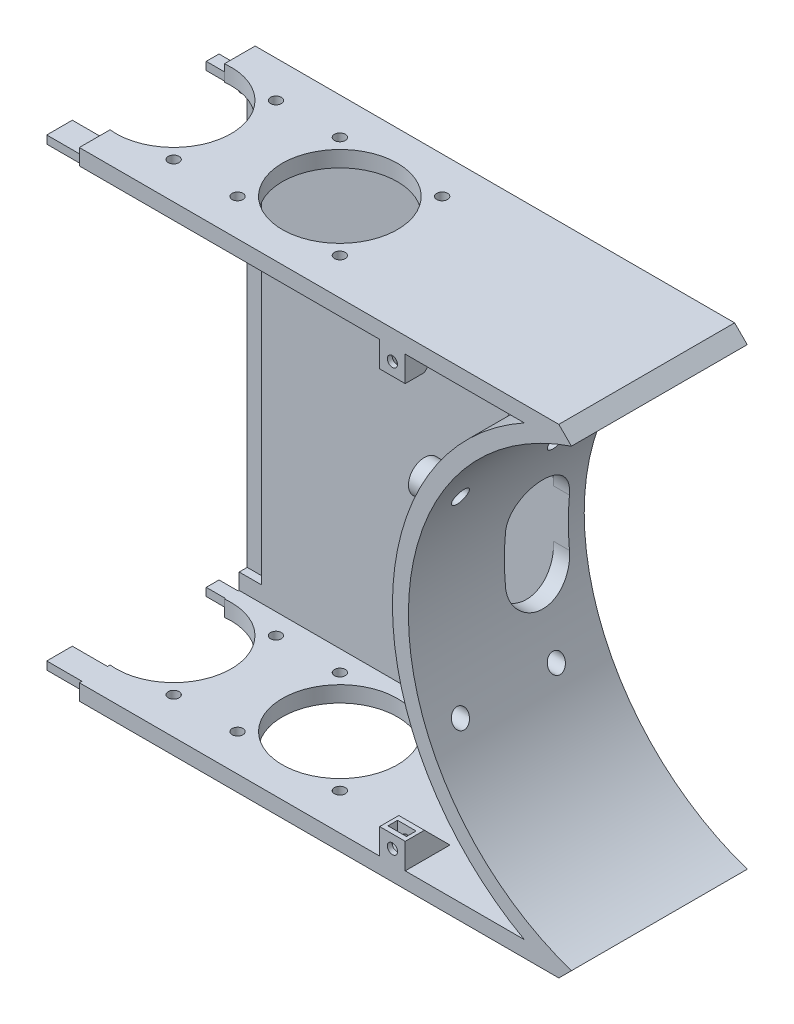
SolidWorks part; units mm, degrees
material "PLA"
ref_plane "Alzado" through (0, 0, 0) normal (0, 0, 1) x (1, 0, 0)
ref_plane "Planta" through (0, 0, 0) normal (0, 1, 0) x (1, 0, 0)
ref_plane "Vista lateral" through (0, 0, 0) normal (1, 0, 0) x (0, 0, -1)
sketch "Croquis1" plane through (0, 0, 0) normal (0, 0, 1) x (1, 0, 0)
  line L0 (-327.9437, 75) -> (-327.9437, -75)
  line L1 (-327.9437, 75) -> (-27.9437, 75)
  line L2 (-27.9437, 75) -> (-24, 71.0563)
  line L3 (-327.9437, -75) -> (-27.9437, -75)
  line L4 (-27.9437, -75) -> (-24, -71.0563)
  circle A0 centre (0, 0) radius 75 construction
  arc A1 (-24, 71.0563) -> (-24, -71.0563) centre (0, 0) ccw
  point P6 (-327.9437, 0)
  point P11 (-75, 0)
  dimension "D1" = 150
  dimension "D2" = 150
  dimension "D3" = 300
  dimension "D4" = 135
  dimension "D5" = 24
extrude "Saliente-Extruir1" add sketch "Croquis1" along normal blind 55
sketch "Croquis2" plane through (0, 0, 55) normal (0, 0, 1) x (1, 0, 0)
  line L2 (-27.9437, 70) -> (-327.9437, 70)
  line L3 (-38.7298, 70) -> (-322.9437, 70)
  line L5 (-322.9437, 75) -> (-322.9437, -75)
  line L6 (-322.9437, 70) -> (-322.9437, -70)
  line L8 (-327.9437, -70) -> (-27.9437, -70)
  line L9 (-322.9437, -70) -> (-38.7298, -70)
  arc A2 (-25.6, 75.7934) -> (-25.6, -75.7934) centre (0, 0) ccw
  arc A3 (-38.7298, 70) -> (-38.7298, -70) centre (0, 0) ccw
  dimension "D1" = 5
  dimension "D2" = 5
  dimension "D3" = 5
  dimension "D4" = 5
extrude "Cortar-Extruir1" cut sketch "Croquis2" against normal blind 50
sketch "Croquis3" plane through (0, 0, 0) normal (1, 0, 0) x (0, 0, -1)
  line L0 (-15, 7.5) -> (-15, -7.5) construction
  line L1 (-5, 7.5) -> (-5, -7.5)
  line L2 (-25, 7.5) -> (-25, -7.5)
  line L3 (-5, 70) -> (-5, -70) construction
  arc A0 (-5, 7.5) -> (-25, 7.5) centre (-15, 7.5) ccw
  arc A1 (-25, -7.5) -> (-5, -7.5) centre (-15, -7.5) ccw
  point P2 (-15, 0)
  dimension "D2" = 10
  dimension "D1" = 15
extrude "Cortar-Extruir2" cut sketch "Croquis3" against normal blind 82
sketch "Croquis4" plane through (0, 0, 0) normal (1, 0, 0) x (0, 0, -1)
  line L0 (-15, 30) -> (-15, -30) construction
  line L1 (-15, 30) -> (-45, 30) construction
  line L2 (-45, 30) -> (-45, -30) construction
  line L3 (-15, -30) -> (-45, -30) construction
  line L4 (-15, 30) -> (-45, -30) construction
  line L5 (-45, 30) -> (-15, -30) construction
  circle A0 centre (-45, -30) radius 2.6
  circle A1 centre (-15, -30) radius 2.6
  circle A2 centre (-15, 30) radius 2.6
  circle A3 centre (-45, 30) radius 2.6
  point P0 (-30, 0)
  dimension "D3" = 5.2
  dimension "D1" = 60
  dimension "D2" = 30
  dimension "D4" = 30
extrude "Cortar-Extruir3" cut sketch "Croquis4" against normal blind 82
ref_plane "Plano1" through (-80, 0, 0) normal (-1, 0, 0) x (0, 0, 1)
sketch "Croquis5" plane through (-80, 0, 0) normal (-1, 0, 0) x (0, 0, 1)
  circle A0 centre (45, -30) radius 2.6 construction
  circle A1 centre (15, -30) radius 2.6 construction
  circle A2 centre (45, 30) radius 2.6 construction
  circle A3 centre (15, 30) radius 2.6 construction
  circle A4 centre (45, -30) radius 2.6
  circle A5 centre (15, -30) radius 2.6
  circle A6 centre (45, 30) radius 2.6
  circle A7 centre (15, 30) radius 2.6
  circle A8 centre (45, 30) radius 5
  circle A9 centre (15, 30) radius 5
  circle A10 centre (45, -30) radius 5
  circle A11 centre (15, -30) radius 5
  dimension "D1" = 10
extrude "Saliente-Extruir2" add sketch "Croquis5" against normal up to surface (5.838 mm away) up to face at (-73.907, -30.6228, 47.5243)
sketch "Croquis6" plane through (0, 0, 5) normal (0, 0, 1) x (1, 0, 0)
  line L0 (-322.9437, 70) -> (-322.9437, -70) construction
  line L1 (-97.9437, -48) -> (-322.9437, -48) construction
  line L2 (-97.9437, -48) -> (-97.9437, 48) construction
  line L3 (-97.9437, 48) -> (-322.9437, 48) construction
  line L4 (-322.9437, -48) -> (-322.9437, 48) construction
  line L5 (-97.9437, -48) -> (-322.9437, 48) construction
  line L6 (-97.9437, 48) -> (-322.9437, -48) construction
  circle A0 centre (-302.9437, 44) radius 1.6
  circle A1 centre (-317.9437, -44) radius 1.6
  circle A2 centre (-190.9437, 43) radius 1.6
  circle A3 centre (-102.9437, 43) radius 1.6
  circle A4 centre (-102.9437, -43) radius 1.6
  point P0 (-210.4437, 0)
  dimension "D3" = 3.2
  dimension "D1" = 225
  dimension "D2" = 96
  dimension "D4" = 4
  dimension "D5" = 20
  dimension "D6" = 93
  dimension "D7" = 5
  dimension "D8" = 5
  dimension "D9" = 5
  dimension "D10" = 5
  dimension "D11" = 5
  dimension "D12" = 4
  dimension "D13" = 5
extrude "Cortar-Extruir4" cut sketch "Croquis6" against normal blind 82
sketch "Croquis7" plane through (-327.9437, 0, 0) normal (-1, 0, 0) x (0, 0, 1)
  line L0 (55, 75) -> (55, -75) construction
  line L1 (21.3, 43.8) -> (32.5, 43.8)
  line L2 (21.3, 43.8) -> (21.3, 34.3)
  line L3 (21.3, 34.3) -> (32.5, 34.3)
  line L4 (32.5, 43.8) -> (32.5, 34.3)
  line L5 (21.3, 43.8) -> (32.5, 34.3) construction
  line L6 (21.3, 34.3) -> (32.5, 43.8) construction
  line L7 (55, 75) -> (0, 75) construction
  point P0 (26.9, 39.05)
  dimension "D1" = 22.5
  dimension "D2" = 31.2
  dimension "D3" = 11.2
  dimension "D4" = 9.5
extrude "Cortar-Extruir5" cut sketch "Croquis7" against normal blind 13
sketch "Croquis8" plane through (-327.9437, 0, 0) normal (-1, 0, 0) x (0, 0, 1)
  line L0 (0, 75) -> (0, -75) construction
  line L1 (19.7, -8) -> (8.5, -8)
  line L2 (19.7, -8) -> (19.7, 4.4)
  line L3 (19.7, 4.4) -> (8.5, 4.4)
  line L4 (8.5, -8) -> (8.5, 4.4)
  line L5 (19.7, -8) -> (8.5, 4.4) construction
  line L6 (19.7, 4.4) -> (8.5, -8) construction
  line L7 (55, -75) -> (0, -75) construction
  point P0 (14.1, -1.8)
  point P9 (14.1, -8)
  dimension "D1" = 8.5
  dimension "D2" = 67
  dimension "D3" = 11.2
  dimension "D4" = 12.4
extrude "Cortar-Extruir6" cut sketch "Croquis8" against normal blind 13
sketch "Croquis9" plane through (0, 0, 5) normal (0, 0, 1) x (1, 0, 0)
  circle A0 centre (-302.9437, 44) radius 4
  circle A1 centre (-317.9437, -44) radius 4
  circle A2 centre (-190.9437, 43) radius 4
  circle A3 centre (-102.9437, 43) radius 4
  circle A4 centre (-102.9437, -43) radius 4
  circle A5 centre (-190.9437, 43) radius 1.6 construction
  circle A6 centre (-317.9437, -44) radius 1.6 construction
  circle A7 centre (-102.9437, 43) radius 1.6 construction
  circle A8 centre (-102.9437, -43) radius 1.6 construction
  circle A9 centre (-102.9437, -43) radius 1.6
  circle A10 centre (-102.9437, 43) radius 1.6
  circle A11 centre (-317.9437, -44) radius 1.6
  circle A12 centre (-190.9437, 43) radius 1.6
  circle A13 centre (-302.9437, 44) radius 1.6 construction
  circle A14 centre (-302.9437, 44) radius 1.6
  dimension "D1" = 8
extrude "Saliente-Extruir3" add sketch "Croquis9" along normal blind 14.8
sketch "Croquis10" plane through (0, -75, 0) normal (0, -1, 0) x (1, 0, 0)
  line L0 (-159.9437, 11.5) -> (-191.9437, 11.5) construction
  line L1 (-159.9437, 11.5) -> (-159.9437, 43.5) construction
  line L2 (-159.9437, 43.5) -> (-191.9437, 43.5) construction
  line L3 (-191.9437, 11.5) -> (-191.9437, 43.5) construction
  line L4 (-159.9437, 11.5) -> (-191.9437, 43.5) construction
  line L5 (-159.9437, 43.5) -> (-191.9437, 11.5) construction
  line L6 (-107.9437, 11.5) -> (-139.9437, 11.5) construction
  line L7 (-107.9437, 11.5) -> (-107.9437, 43.5) construction
  line L8 (-107.9437, 43.5) -> (-139.9437, 43.5) construction
  line L9 (-139.9437, 11.5) -> (-139.9437, 43.5) construction
  line L10 (-107.9437, 11.5) -> (-139.9437, 43.5) construction
  line L11 (-107.9437, 43.5) -> (-139.9437, 11.5) construction
  line L12 (-327.9437, 55) -> (-327.9437, 0) construction
  line L13 (-27.9437, 55) -> (-27.9437, 0) construction
  circle A0 centre (-191.9437, 43.5) radius 1.7
  circle A1 centre (-159.9437, 43.5) radius 1.7
  circle A2 centre (-191.9437, 11.5) radius 1.7
  circle A3 centre (-159.9437, 11.5) radius 1.7
  circle A4 centre (-139.9437, 43.5) radius 1.7
  circle A5 centre (-107.9437, 43.5) radius 1.7
  circle A6 centre (-139.9437, 11.5) radius 1.7
  circle A7 centre (-107.9437, 11.5) radius 1.7
  circle A12 centre (-175.9437, 27.5) radius 18
  circle A13 centre (-123.9437, 27.5) radius 18
  point P4 (-175.9437, 27.5)
  point P13 (-123.9437, 27.5)
  point P20 (-327.9437, 27.5)
  dimension "D3" = 3.4
  dimension "D6" = 3.4
  dimension "D9" = 36
  dimension "D1" = 32
  dimension "D2" = 32
  dimension "D4" = 32
  dimension "D5" = 32
  dimension "D7" = 20
  dimension "D8" = 80
extrude "Cortar-Extruir7" cut sketch "Croquis10" against normal blind 14.8
mirror "Simetría1" about plane through (0, 0, 0) normal (0, 1, 0) of "Cortar-Extruir7"
ref_plane "Plano2" through (0, 0, 13) normal (0, 0, 1) x (1, 0, 0)
sketch "Croquis11" plane through (0, 0, 13) normal (0, 0, 1) x (1, 0, 0)
  line L0 (-301.2687, 46.9012) -> (-296.5962, 46.9012)
  line L1 (-299.5937, 44) -> (-301.2687, 46.9012) construction
  line L2 (-301.2687, 46.9012) -> (-304.6187, 46.9012)
  line L3 (-304.6187, 46.9012) -> (-306.2937, 44)
  line L4 (-306.2937, 44) -> (-304.6187, 41.0988)
  line L5 (-304.6187, 41.0988) -> (-301.2687, 41.0988)
  line L6 (-301.2687, 41.0988) -> (-299.5937, 44) construction
  line L7 (-314.5937, -44) -> (-316.2687, -41.0988) construction
  line L8 (-316.2687, -41.0988) -> (-319.6187, -41.0988)
  line L9 (-319.6187, -41.0988) -> (-321.2937, -44)
  line L10 (-321.2937, -44) -> (-319.6187, -46.9012)
  line L11 (-319.6187, -46.9012) -> (-316.2687, -46.9012)
  line L12 (-316.2687, -46.9012) -> (-314.5937, -44) construction
  line L13 (-187.5937, 43) -> (-189.2687, 45.9012)
  line L14 (-189.2687, 45.9012) -> (-192.6187, 45.9012)
  line L15 (-192.6187, 45.9012) -> (-194.2937, 43) construction
  line L16 (-194.2937, 43) -> (-192.6187, 40.0988) construction
  line L17 (-192.6187, 40.0988) -> (-189.2687, 40.0988)
  line L18 (-189.2687, 40.0988) -> (-187.5937, 43)
  line L19 (-99.5937, 43) -> (-101.2687, 45.9012)
  line L20 (-101.2687, 45.9012) -> (-104.6187, 45.9012)
  line L21 (-104.6187, 45.9012) -> (-106.2937, 43) construction
  line L22 (-106.2937, 43) -> (-104.6187, 40.0988) construction
  line L23 (-104.6187, 40.0988) -> (-101.2687, 40.0988)
  line L24 (-101.2687, 40.0988) -> (-99.5937, 43)
  line L25 (-99.5937, -43) -> (-101.2687, -40.0988)
  line L26 (-101.2687, -40.0988) -> (-104.6187, -40.0988)
  line L27 (-104.6187, -40.0988) -> (-106.2937, -43) construction
  line L28 (-106.2937, -43) -> (-104.6187, -45.9012) construction
  line L29 (-104.6187, -45.9012) -> (-101.2687, -45.9012)
  line L30 (-101.2687, -45.9012) -> (-99.5937, -43)
  line L31 (-296.5962, 46.9012) -> (-296.5962, 41.0988)
  line L32 (-296.5962, 41.0988) -> (-301.2687, 41.0988)
  line L33 (-192.6187, 45.9012) -> (-196.6834, 45.9012)
  line L34 (-196.6834, 45.9012) -> (-196.6834, 40.0988)
  line L35 (-196.6834, 40.0988) -> (-192.6187, 40.0988)
  line L36 (-104.6187, 45.9012) -> (-110.7706, 45.9012)
  line L37 (-110.7706, 45.9012) -> (-110.7706, 40.0988)
  line L38 (-110.7706, 40.0988) -> (-104.6187, 40.0988)
  line L39 (-104.6187, -40.0988) -> (-109.0472, -40.0988)
  line L40 (-109.0472, -40.0988) -> (-109.1678, -45.9012)
  line L41 (-109.1678, -45.9012) -> (-104.6187, -45.9012)
  line L42 (-316.2687, -46.9012) -> (-310.7216, -46.9012)
  line L43 (-310.7216, -46.9012) -> (-310.7216, -41.0988)
  line L44 (-310.7216, -41.0988) -> (-316.2687, -41.0988)
  line L45 (-38.7298, 70) -> (-322.9437, 70) construction
  line L46 (-322.9437, -70) -> (-38.7298, -70) construction
  circle A0 centre (-302.9437, 44) radius 3.35 construction
  circle A1 centre (-317.9437, -44) radius 3.35 construction
  circle A2 centre (-190.9437, 43) radius 3.35 construction
  circle A3 centre (-102.9437, 43) radius 3.35 construction
  circle A4 centre (-102.9437, -43) radius 3.35 construction
  dimension "D1" = 6.7
extrude "Cortar-Extruir8" cut sketch "Croquis11" against normal blind 1.5 and the other way blind 1.5
sketch "Croquis12" plane through (0, 0, 0) normal (0, 1, 0) x (1, 0, 0)
  line L0 (-322.9437, -41) -> (-322.9437, -55)
  line L1 (-322.9437, -55) -> (-314.9437, -55)
  line L6 (-27.9437, -55) -> (-327.9437, -55) construction
  line L7 (-322.9437, -19.7) -> (-322.9437, -8.5) construction
  line L8 (-314.9437, -55) -> (-314.9437, -49)
  line L9 (-314.9437, -49) -> (-322.9437, -41)
  dimension "D1" = 8
  dimension "D2" = 45
  dimension "D3" = 6
extrude "Saliente-Extruir4" add sketch "Croquis12" along normal blind 4 and the other way blind 4
sketch "Croquis14" plane through (-80, 0, 0) normal (-1, 0, 0) x (0, 0, 1)
  line L0 (55, 70) -> (55, 62)
  line L1 (55, -70) -> (55, 70) construction
  line L3 (5, 70) -> (55, 70) construction
  line L4 (41, 70) -> (55, 70)
  line L5 (55, -70) -> (55, -62)
  line L7 (5, -70) -> (55, -70) construction
  line L8 (41, -70) -> (55, -70)
  line L9 (55, 62) -> (49, 62)
  line L10 (49, 62) -> (41, 70)
  line L11 (41, -70) -> (49, -62)
  line L12 (49, -62) -> (55, -62)
  dimension "D2" = 8
  dimension "D3" = 45
  dimension "D4" = 8
  dimension "D5" = 6
extrude "Saliente-Extruir5" add sketch "Croquis14" along normal blind 4 and the other way blind 4
sketch "Croquis13" plane through (0, 0, 55) normal (0, 0, 1) x (1, 0, 0)
  line L0 (-322.9437, 4) -> (-314.9437, -4) construction
  line L1 (-314.9437, 4) -> (-322.9437, -4) construction
  line L2 (-84, 70) -> (-76, 62) construction
  line L4 (-76, 70) -> (-84, 62) construction
  line L6 (-84, -62) -> (-76, -70) construction
  line L7 (-84, -70) -> (-76, -62) construction
  line L8 (-76, -70) -> (-76, -62) construction
  line L9 (-84, -70) -> (-84, -62) construction
  circle A0 centre (-318.9437, 0) radius 1.6
  circle A2 centre (-80, -66) radius 1.6
  circle A3 centre (-80, 66) radius 1.6
  dimension "D1" = 3.2
extrude "Cortar-Extruir9" cut sketch "Croquis13" against normal blind 14
ref_plane "Plano3" through (-160, 0, 0) normal (-1, 0, 0) x (0, 0, 1)
ref_plane "Plano4" through (0, 0, 52) normal (0, 0, 1) x (1, 0, 0)
mirror "Simetría2" about plane through (-160, 0, 0) normal (-1, 0, 0) of "Cortar-Extruir9", "Saliente-Extruir5"
sketch "Croquis17" plane through (0, 0, 52) normal (0, 0, 1) x (1, 0, 0)
  line L0 (-322.9437, 70) -> (-322.9437, 4) construction
  line L1 (-315.5937, 0) -> (-317.2687, 2.9012) construction
  line L2 (-317.2687, 2.9012) -> (-320.6187, 2.9012)
  line L3 (-320.6187, 2.9012) -> (-322.2937, 0)
  line L4 (-322.2937, 0) -> (-320.6187, -2.9012)
  line L5 (-320.6187, -2.9012) -> (-317.2687, -2.9012)
  line L6 (-317.2687, -2.9012) -> (-315.5937, 0) construction
  line L7 (-240, -62.65) -> (-242.9012, -64.325) construction
  line L8 (-242.9012, -64.325) -> (-242.9012, -67.675)
  line L9 (-242.9012, -67.675) -> (-240, -69.35)
  line L10 (-240, -69.35) -> (-237.0988, -67.675)
  line L11 (-237.0988, -67.675) -> (-237.0988, -64.325)
  line L12 (-237.0988, -64.325) -> (-240, -62.65) construction
  line L13 (-80, -62.65) -> (-82.9012, -64.325) construction
  line L14 (-82.9012, -64.325) -> (-82.9012, -67.675)
  line L15 (-82.9012, -67.675) -> (-80, -69.35)
  line L16 (-80, -69.35) -> (-77.0988, -67.675)
  line L17 (-77.0988, -67.675) -> (-77.0988, -64.325)
  line L18 (-77.0988, -64.325) -> (-80, -62.65) construction
  line L19 (-80, 62.65) -> (-77.0988, 64.325) construction
  line L20 (-77.0988, 64.325) -> (-77.0988, 67.675)
  line L21 (-77.0988, 67.675) -> (-80, 69.35)
  line L22 (-80, 69.35) -> (-82.9012, 67.675)
  line L23 (-82.9012, 67.675) -> (-82.9012, 64.325)
  line L24 (-82.9012, 64.325) -> (-80, 62.65) construction
  line L25 (-240, 62.65) -> (-237.0988, 64.325) construction
  line L26 (-237.0988, 64.325) -> (-237.0988, 67.675)
  line L27 (-237.0988, 67.675) -> (-240, 69.35)
  line L28 (-240, 69.35) -> (-242.9012, 67.675)
  line L29 (-242.9012, 67.675) -> (-242.9012, 64.325)
  line L30 (-242.9012, 64.325) -> (-240, 62.65) construction
  line L31 (-322.9437, -70) -> (-244, -70) construction
  line L32 (-317.2687, 2.9012) -> (-310.6187, 2.9012)
  line L33 (-310.6187, 2.9012) -> (-310.6187, -2.9012)
  line L34 (-310.6187, -2.9012) -> (-317.2687, -2.9012)
  line L35 (-242.9012, 64.325) -> (-242.9012, 57.675)
  line L36 (-242.9012, 57.675) -> (-237.0988, 57.675)
  line L37 (-237.0988, 57.675) -> (-237.0988, 64.325)
  line L38 (-82.9012, 64.325) -> (-82.9012, 57.675)
  line L39 (-82.9012, 57.675) -> (-76.8873, 57.675)
  line L40 (-76.8873, 57.675) -> (-77.0988, 64.325)
  line L41 (-82.9012, -64.325) -> (-82.9012, -57.675)
  line L42 (-82.9012, -57.675) -> (-77.0988, -57.675)
  line L43 (-77.0988, -57.675) -> (-77.0988, -64.325)
  line L44 (-242.9012, -64.325) -> (-242.9012, -57.675)
  line L45 (-242.9012, -57.675) -> (-237.0988, -57.675)
  line L46 (-237.0988, -57.675) -> (-237.0988, -64.325)
  circle A0 centre (-318.9437, 0) radius 3.35 construction
  circle A1 centre (-240, -66) radius 3.35 construction
  circle A2 centre (-80, -66) radius 3.35 construction
  circle A3 centre (-80, 66) radius 3.35 construction
  circle A4 centre (-240, 66) radius 3.35 construction
  dimension "D1" = 6.7
  dimension "D2" = 10
extrude "Cortar-Extruir10" cut sketch "Croquis17" against normal blind 1.5 and the other way blind 1.5
sketch "Croquis18" plane through (0, 0, 0) normal (0, 0, 1) x (1, 0, 0)
  line L0 (-327.9437, 75) -> (-327.9437, -75) construction
  line L1 (-177.9437, -100) -> (-337.9437, -100)
  line L2 (-177.9437, -100) -> (-177.9437, 100)
  line L3 (-177.9437, 100) -> (-337.9437, 100)
  line L4 (-337.9437, -100) -> (-337.9437, 100)
  line L5 (-177.9437, -100) -> (-337.9437, 100) construction
  line L6 (-177.9437, 100) -> (-337.9437, -100) construction
  line L7 (-322.9437, 70) -> (-322.9437, 4) construction
  point P0 (-257.9437, 0)
  point P10 (0, 0)
  dimension "D1" = 150
  dimension "D2" = 65
  dimension "D3" = 200
extrude "Cortar-Extruir11" cut sketch "Croquis18" along normal blind 122
sketch "Croquis19" plane through (0, -70, 0) normal (0, 1, 0) x (1, 0, 0)
  line L0 (-177.9437, -55) -> (-177.9437, -45.3885) construction
  line L1 (-166.9437, -46.1943) -> (-188.9437, -46.1943)
  line L2 (-166.9437, -46.1943) -> (-166.9437, -54.1943)
  line L3 (-166.9437, -54.1943) -> (-188.9437, -54.1943)
  line L4 (-188.9437, -46.1943) -> (-188.9437, -54.1943)
  line L5 (-166.9437, -46.1943) -> (-188.9437, -54.1943) construction
  line L6 (-166.9437, -54.1943) -> (-188.9437, -46.1943) construction
  line L7 (-177.9437, -9.6115) -> (-177.9437, -5) construction
  line L8 (-171.9437, -5.3057) -> (-183.9437, -5.3057)
  line L9 (-171.9437, -5.3057) -> (-171.9437, -9.3057)
  line L10 (-171.9437, -9.3057) -> (-183.9437, -9.3057)
  line L11 (-183.9437, -5.3057) -> (-183.9437, -9.3057)
  line L12 (-171.9437, -5.3057) -> (-183.9437, -9.3057) construction
  line L13 (-171.9437, -9.3057) -> (-183.9437, -5.3057) construction
  point P0 (-177.9437, -50.1943)
  point P7 (-177.9437, -7.3057)
  dimension "D1" = 8
  dimension "D2" = 4
  dimension "D3" = 12
  dimension "D4" = 22
extrude "Saliente-Extruir6" add sketch "Croquis19" against normal blind 2.5
mirror "Simetría3" about plane through (0, 0, 0) normal (0, 1, 0) of "Saliente-Extruir6"
sketch "Croquis21" plane through (0, 0, 5) normal (0, 0, 1) x (1, 0, 0)
  line L0 (-177.9437, 70) -> (-177.9437, -70) construction
  line L1 (-170.9437, -65) -> (-184.9437, -65)
  line L2 (-170.9437, -65) -> (-170.9437, 65)
  line L3 (-170.9437, 65) -> (-184.9437, 65)
  line L4 (-184.9437, -65) -> (-184.9437, 65)
  line L5 (-170.9437, -65) -> (-184.9437, 65) construction
  line L6 (-170.9437, 65) -> (-184.9437, -65) construction
  point P0 (-177.9437, 0)
  dimension "D1" = 130
  dimension "D2" = 14
extrude "Cortar-Extruir12" cut sketch "Croquis21" against normal blind 2.5
